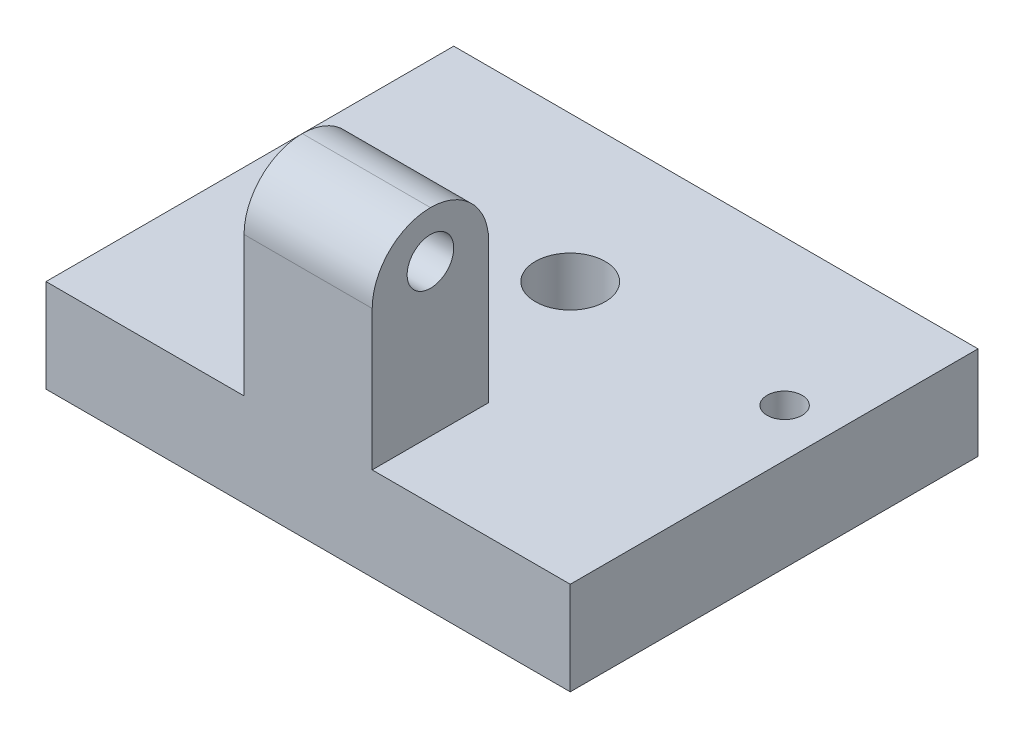
SolidWorks part; units mm, degrees
note: The reader was unsure of these and kept them because the rebuilt part matched: shared geometry of "Sketch4<3>".
ref_plane "Front Plane" through (0, 0, 0) normal (0, 0, 1) x (1, 0, 0)
ref_plane "Top Plane" through (0, 0, 0) normal (0, 1, 0) x (1, 0, 0)
ref_plane "Right Plane" through (0, 0, 0) normal (1, 0, 0) x (0, 0, -1)
sketch "Sketch2" plane through (0, 0, 0) normal (0, 1, 0) x (1, 0, 0)
  line L0 (0, 17.5) -> (0, -17.5) construction
  line L1 (-22.5, -17.5) -> (22.5, -17.5)
  line L2 (-22.5, -17.5) -> (-22.5, 17.5)
  line L3 (-22.5, 17.5) -> (22.5, 17.5)
  line L4 (22.5, -17.5) -> (22.5, 17.5)
  line L5 (-22.5, -17.5) -> (22.5, 17.5) construction
  line L6 (-22.5, 17.5) -> (22.5, -17.5) construction
  circle A0 centre (0, 5) radius 3
  circle A3 centre (-18.4, 5) radius 1.5
  circle A4 centre (18.4, 5) radius 1.5
  point P10 (0, 0)
  dimension "D3" = 6
  dimension "D4" = 5
  dimension "D6" = 18.4
  dimension "D5" = 3
  dimension "D1" = 45
  dimension "D2" = 35
extrude "Boss-Extrude1" add sketch "Sketch2" along normal blind 5
sketch "Sketch4" plane through (0, 5, 0) normal (0, 1, 0) x (1, 0, 0)
  line L0 (-22.5, -17.5) -> (22.5, -17.5) construction
  line L1 (15, -17.5) -> (-15, -17.5)
  line L7 (5.5, -17.5) -> (-5.5, -17.5)
  line L8 (5.5, -17.5) -> (5.5, -7.5)
  line L9 (5.5, -7.5) -> (-5.5, -7.5)
  line L10 (-5.5, -17.5) -> (-5.5, -7.5)
  point P14 (0, -7.5)
  dimension "D1" = 10
  dimension "D2" = 5.5
extrude "Boss-Extrude2" add sketch "Sketch4" along normal blind 3
extrude "Boss-Extrude3" add sketch "Sketch4<3>" along normal blind 20 contours L10 L1 L8 L9
sketch "Sketch4<3>" plane through (0, 5, 0) normal (0, 1, 0) x (1, 0, 0) same geometry as "Sketch4"
sketch "Sketch5" plane through (5.5, 0, 0) normal (1, 0, 0) x (0, 0, -1)
  line L4 (-17.5, 8) -> (-7.5, 8)
  line L5 (-7.5, 8) -> (-7.5, 25)
  line L6 (-7.5, 25) -> (-17.5, 25)
  line L7 (-17.5, 25) -> (-17.5, 8)
  line L8 (-17.5, 8) -> (-7.5, 8)
  line L9 (-7.5, 8) -> (-7.5, 25)
  line L10 (-7.5, 25) -> (-17.5, 25)
  line L11 (-17.5, 25) -> (-17.5, 8)
  circle A0 centre (-12.5, 21) radius 2
  point P6 (-12.5, 25)
  dimension "D2" = 4
  dimension "D3" = 4
  dimension "D1" = 0
extrude "Cut-Extrude1" cut sketch "Sketch5" against normal blind 20 contours A0
fillet "Fillet1" radius 5 2 edges at (0, 25, 7.5) (0, 25, 17.5)
